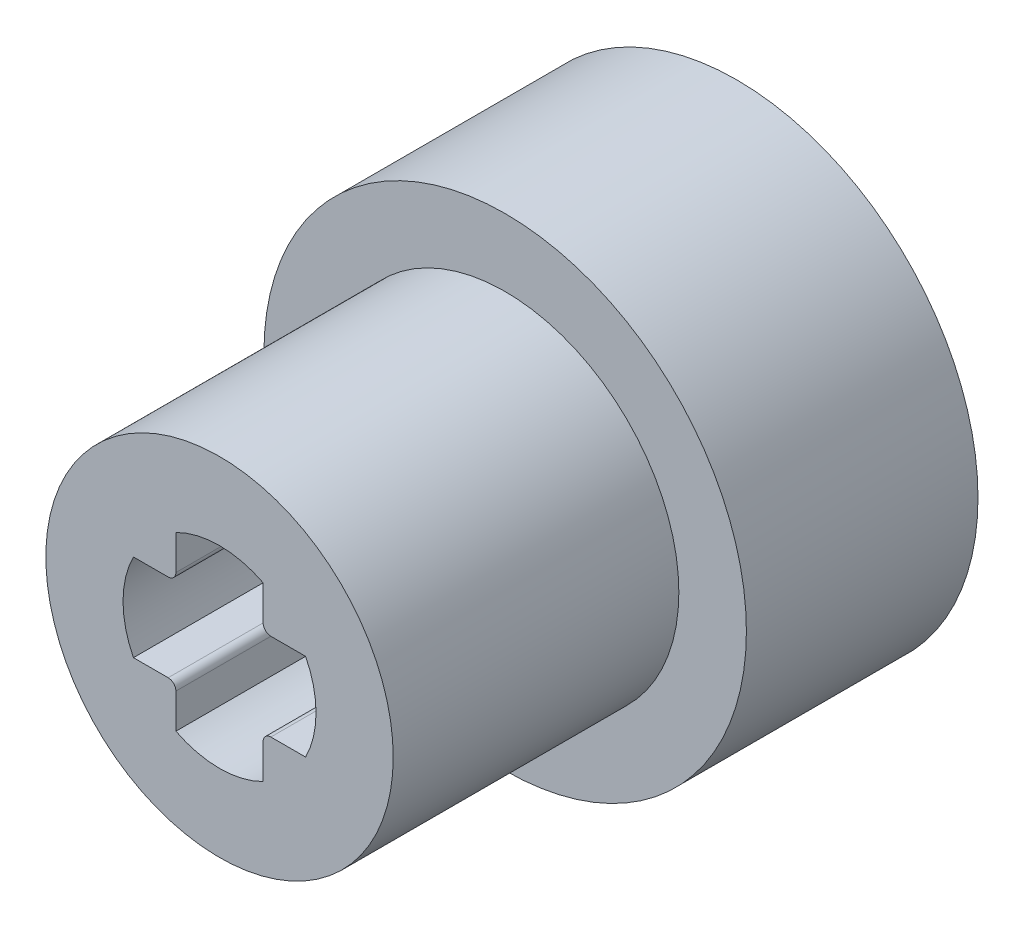
SolidWorks part; units mm, degrees
ref_plane "前视基准面" through (0, 0, 0) normal (0, 0, 1) x (1, 0, 0)
ref_plane "上视基准面" through (0, 0, 0) normal (0, 1, 0) x (1, 0, 0)
ref_plane "右视基准面" through (0, 0, 0) normal (1, 0, 0) x (0, 0, -1)
other "Configuration Table"
sketch "草图1" plane through (0, 0, 0) normal (0, 0, 1) x (1, 0, 0)
  circle A6 centre (0, 0) radius 6.25
  circle A7 centre (0, 0) radius 1.25
  dimension "D1" = 2.5
  dimension "D2" = 5
extrude "凸台-拉伸1" add sketch "草图1" along normal blind 5
extrude "凸台-拉伸2" add sketch "草图1<5>" along normal blind 1 from surface contours A6 starting at face at (6.25, 0, 5)
sketch "草图1<5>" plane through (0, 0, 0) normal (0, 0, 1) x (1, 0, 0) same geometry as "草图1"
sketch "草图2" plane through (0, 0, 6) normal (0, 0, 1) x (1, 0, 0)
  line L1 (-1.13, -2.23) -> (1.13, -2.23)
  line L2 (-1.13, -2.23) -> (-1.13, 2.23)
  line L3 (-1.13, 2.23) -> (1.13, 2.23)
  line L4 (1.13, -2.23) -> (1.13, 2.23)
  line L5 (-1.13, -2.23) -> (1.13, 2.23) construction
  line L6 (-1.13, 2.23) -> (1.13, -2.23) construction
  line L7 (-2.23, -1.13) -> (2.23, -1.13)
  line L8 (-2.23, -1.13) -> (-2.23, 1.13)
  line L9 (-2.23, 1.13) -> (2.23, 1.13)
  line L10 (2.23, -1.13) -> (2.23, 1.13)
  line L11 (-2.23, -1.13) -> (2.23, 1.13) construction
  line L12 (-2.23, 1.13) -> (2.23, -1.13) construction
  circle A0 centre (0, 0) radius 2.5
  circle A1 centre (0, 0) radius 4.5
  dimension "D1" = 5
  dimension "D2" = 2
  dimension "D3" = 1.1
extrude "凸台-拉伸3" add sketch "草图2" along normal blind 7.4 contours A1
extrude "切除-拉伸1" cut sketch "草图2<3>" against normal blind 7.4 from surface contours L10 A0 | L3 A0 | L8 A0 | L1 A0 | L4 L3 L2 L1 | L10 L9 L8 L7 region at (0, -2.3385, 6) region at (-2.3385, 0, 6) region at (2.3385, 0, 6) region at (0, 2.3385, 6) starting at face at (4.5, 0, 13.4)
sketch "草图2<3>" plane through (0, 0, 6) normal (0, 0, 1) x (1, 0, 0) same geometry as "草图2"
fillet "圆角1" radius 0.2 4 edges at (-1.13, -1.13, 9.7) (1.13, -1.13, 9.7) (-1.13, 1.13, 9.7) (1.13, 1.13, 9.7)
